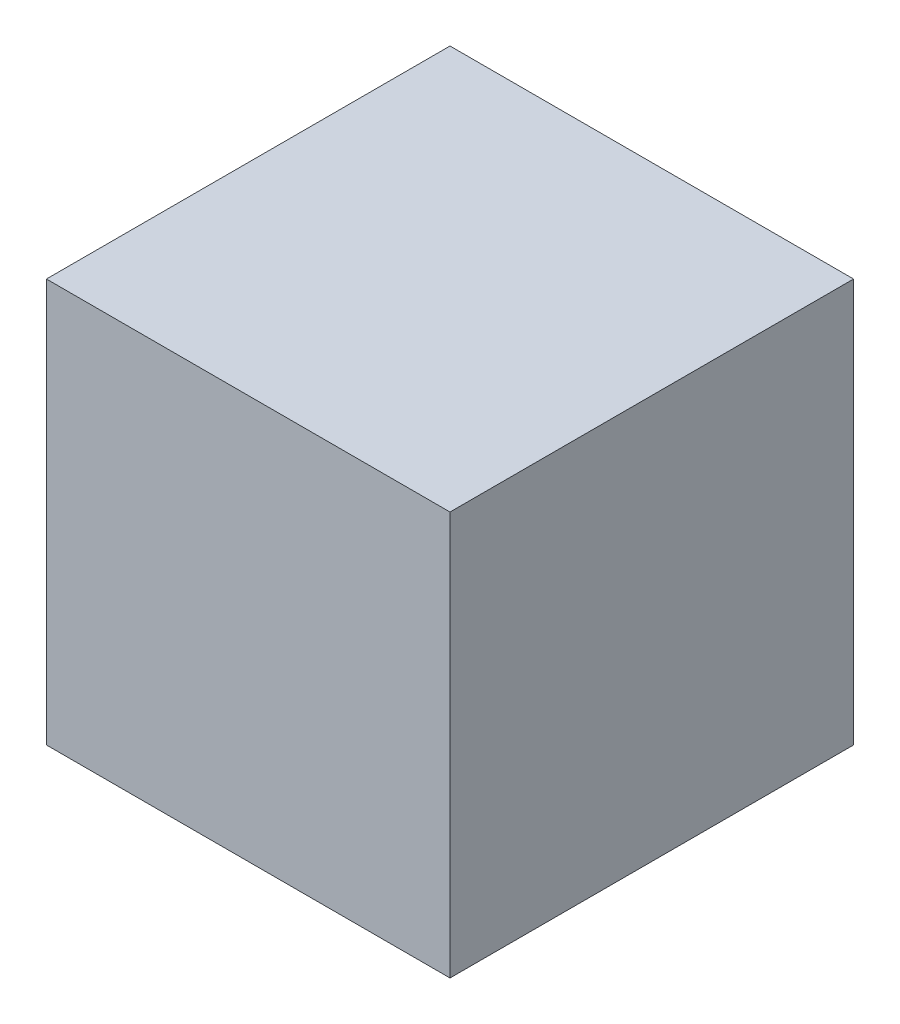
SolidWorks part; units mm, degrees
ref_plane "Plan de face" through (0, 0, 0) normal (0, 0, 1) x (1, 0, 0)
ref_plane "Plan de dessus" through (0, 0, 0) normal (0, 1, 0) x (1, 0, 0)
ref_plane "Plan de droite" through (0, 0, 0) normal (1, 0, 0) x (0, 0, -1)
sketch "Esquisse1" plane through (0, 0, 0) normal (0, 0, 1) x (1, 0, 0)
  line L1 (-40, 40) -> (40, 40)
  line L2 (-40, 40) -> (-40, -40)
  line L3 (-40, -40) -> (40, -40)
  line L4 (40, 40) -> (40, -40)
  line L5 (-40, 40) -> (40, -40) construction
  line L6 (-40, -40) -> (40, 40) construction
  circle A0 centre (0, 0) radius 20
  circle A1 centre (15, 0) radius 1.5
  dimension "D1" = 15
  dimension "D2" = 40
  dimension "D3" = 3
  dimension "D4" = 80
  dimension "D5" = 80
extrude "Boss.-Extru.1" add sketch "Esquisse1" along normal blind 80 contours L2 L3 L4 L1
extrude "Enlèv. mat.-Extru.1" cut sketch "Esquisse1<4>" along normal blind 3 contours A0 A1 region at (-0.0849, 0, 0)
sketch "Esquisse1<4>" plane through (0, 0, 0) normal (0, 0, 1) x (1, 0, 0) same geometry as "Esquisse1"
